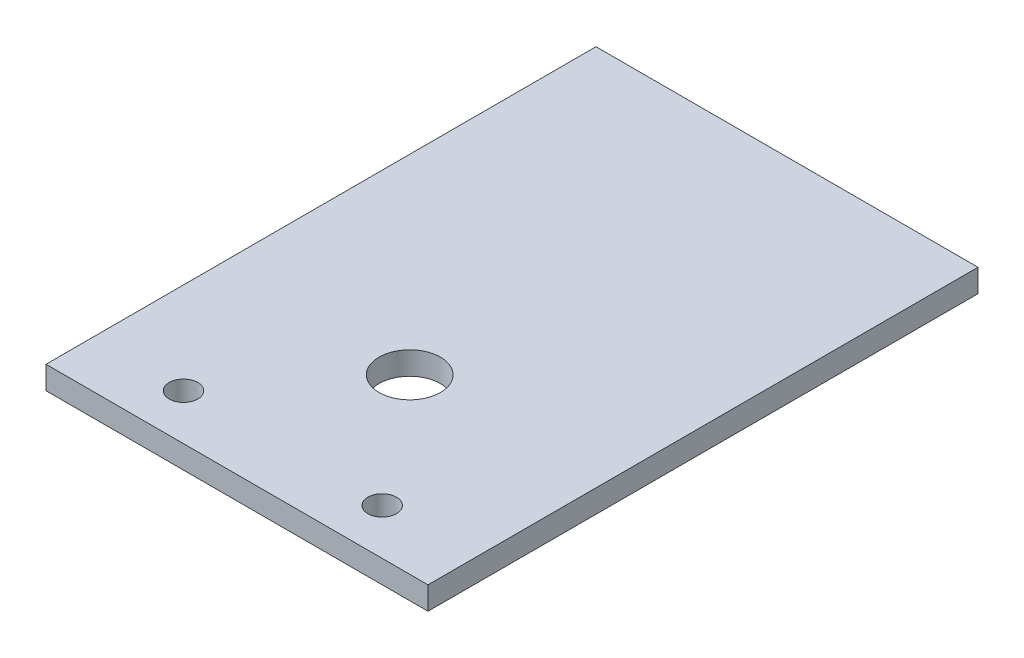
SolidWorks part; units mm, degrees
material "6061 Alloy"
ref_plane "Front Plane" through (0, 0, 0) normal (0, 0, 1) x (1, 0, 0)
ref_plane "Top Plane" through (0, 0, 0) normal (0, 1, 0) x (1, 0, 0)
ref_plane "Right Plane" through (0, 0, 0) normal (1, 0, 0) x (0, 0, -1)
sketch "Sketch1" plane through (0, 0, 0) normal (0, 1, 0) x (1, 0, 0)
  line L1 (-52.925, 76.2) -> (52.925, 76.2)
  line L2 (-52.925, 76.2) -> (-52.925, -76.2)
  line L3 (-52.925, -76.2) -> (52.925, -76.2)
  line L4 (52.925, 76.2) -> (52.925, -76.2)
  line L5 (-52.925, 76.2) -> (52.925, -76.2) construction
  line L6 (-52.925, -76.2) -> (52.925, 76.2) construction
  point P0 (0, 0)
  dimension "D1" = 152.4
  dimension "D2" = 105.85
extrude "Boss-Extrude1" add sketch "Sketch1" along normal blind 6.35
sketch "Sketch2" plane through (0, 6.35, 0) normal (0, 1, 0) x (1, 0, 0)
  line L0 (0, 0) -> (0, -11.2478) construction
  line L1 (0, 0) -> (-15.1024, 0) construction
  line L2 (-52.925, -76.2) -> (52.925, -76.2) construction
  line L3 (-52.925, 76.2) -> (-52.925, -76.2) construction
  circle A0 centre (-27.525, -63.5) radius 3.9688
  circle A1 centre (27.525, -63.5) radius 3.9688
  circle A2 centre (0, -28.34) radius 8.5
  dimension "D1" = 12.7
  dimension "D2" = 25.4
  dimension "D3" = 17
  dimension "D4" = 47.86
extrude "Cut-Extrude1" cut sketch "Sketch2" against normal up to next
